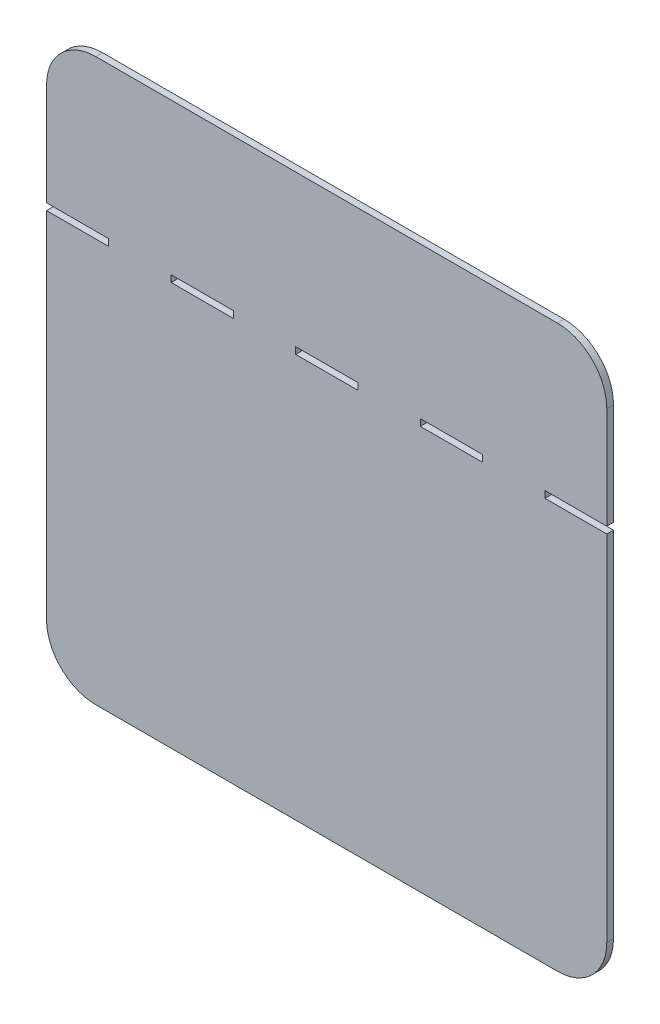
SolidWorks part; units mm, degrees
material "Pine"
ref_plane "Front Plane" through (0, 0, 0) normal (0, 0, 1) x (1, 0, 0)
ref_plane "Top Plane" through (0, 0, 0) normal (0, 1, 0) x (1, 0, 0)
ref_plane "Right Plane" through (0, 0, 0) normal (1, 0, 0) x (0, 0, -1)
sketch "Sketch1" plane through (0, 0, 0) normal (0, 0, 1) x (1, 0, 0)
  line L1 (0, 0) -> (500, 0)
  line L2 (0, 0) -> (0, 501)
  line L3 (0, 501) -> (500, 501)
  line L4 (500, 0) -> (500, 501)
  dimension "D1" = 500
  dimension "D2" = 501
extrude "Boss-Extrude1" add sketch "Sketch1" along normal blind 6
fillet "Fillet1" radius 44 4 edges at (0, 0, 3) (0, 501, 3) (500, 0, 3) (500, 501, 3)
sketch "Sketch2" plane through (0, 0, 0) normal (0, 0, -1) x (-1, 0, 0)
  line L0 (-456, 501) -> (-44, 501) construction
  line L1 (0, 360) -> (-55.5, 360)
  line L2 (0, 360) -> (0, 366)
  line L3 (0, 366) -> (-55.5, 366)
  line L4 (-55.5, 360) -> (-55.5, 366)
  line L5 (0, 457) -> (0, 44) construction
  dimension "D1" = 135
  dimension "D2" = 6
  dimension "D3" = 0
  dimension "D4" = 55.5
extrude "Cut-Extrude1" cut sketch "Sketch2" against normal blind 10
pattern_linear "LPattern1" count 5 spacing 111.2 along (1, 0, 0) of "Cut-Extrude1"
